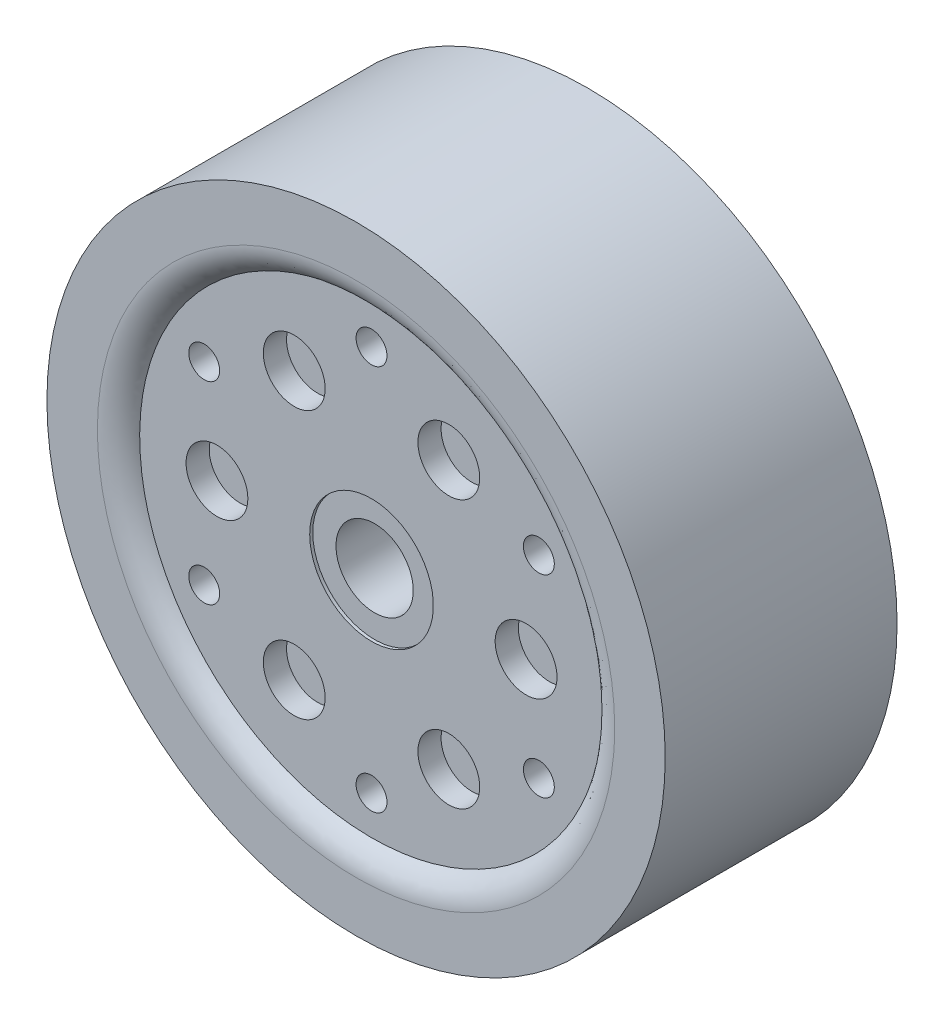
SolidWorks part; units mm, degrees
ref_plane "Plan de face" through (0, 0, 0) normal (0, 0, 1) x (1, 0, 0)
ref_plane "Plan de dessus" through (0, 0, 0) normal (0, 1, 0) x (1, 0, 0)
ref_plane "Plan de droite" through (0, 0, 0) normal (1, 0, 0) x (0, 0, -1)
sketch "Esquisse1" plane through (0, 0, 0) normal (0, 0, 1) x (1, 0, 0)
  circle A0 centre (0, 0) radius 20
  circle A1 centre (0, 0) radius 2.5
  circle A2 centre (0, 0) radius 4
  circle A4 centre (0, 0) radius 15
  circle A5 centre (0, 0) radius 17
extrude "Boss.-Extru.1" add sketch "Esquisse1" along normal blind 7.5 contours A0 A5 | A5 A4 region at (-19.4343, 0, 0) region at (-16.5192, 0, 0)
extrude "Boss.-Extru.2" add sketch "Esquisse1<3>" along normal blind 6.5 contours A4 region at (-14.5757, 0, 0)
sketch "Esquisse1<3>" plane through (0, 0, 0) normal (0, 0, 1) x (1, 0, 0) same geometry as "Esquisse1"
extrude "Boss.-Extru.3" add sketch "Esquisse1<6>" along normal blind 6.3 contours A2 A1 region at (-3.8869, 0, 0)
sketch "Esquisse1<6>" plane through (0, 0, 0) normal (0, 0, 1) x (1, 0, 0) same geometry as "Esquisse1"
fillet "Congé1" radius 2 1 edges at (15, 0, 7.5) first distance on face at (20, 0, 7.5)
sketch "Esquisse3" plane through (0, 0, 6.5) normal (0, 0, 1) x (1, 0, 0)
  line L0 (0, 0) -> (0, 12.5) construction
  line L1 (0, 0) -> (0, -12.5) construction
  line L2 (0, 0) -> (-10.8253, -6.25) construction
  line L3 (0, 0) -> (10.8253, -6.25) construction
  line L4 (0, 0) -> (10.8253, 6.25) construction
  line L5 (0, 0) -> (-10.8253, 6.25) construction
  circle A1 centre (0, 0) radius 12.5 construction
  circle A2 centre (0, 12.5) radius 1
  circle A3 centre (-10.8253, 6.25) radius 1
  circle A4 centre (-10.8253, -6.25) radius 1
  circle A5 centre (0, -12.5) radius 1
  circle A6 centre (10.8253, -6.25) radius 1
  circle A7 centre (10.8253, 6.25) radius 1
  dimension "D1" = 60
  dimension "D2" = 60
  dimension "D3" = 60
sketch "Esquisse4" plane through (0, 0, 6.5) normal (0, 0, 1) x (1, 0, 0)
  line L0 (0, 0) -> (10, 0) construction
  line L1 (10, 0) -> (-10, 0) construction
  line L2 (0, 0) -> (-5, 8.6603) construction
  line L3 (-5, 8.6603) -> (0, 0) construction
  line L4 (0, 0) -> (5, 8.6603) construction
  line L5 (5, 8.6603) -> (0, 0) construction
  line L6 (0, 0) -> (10, 0) construction
  line L7 (10, 0) -> (0, 0) construction
  line L8 (0, 0) -> (5, -8.6603) construction
  line L9 (5, -8.6603) -> (0, 0) construction
  line L10 (0, 0) -> (-5, -8.6603) construction
  circle A0 centre (0, 0) radius 10 construction
  circle A1 centre (-10, 0) radius 2
  circle A2 centre (-5, 8.6603) radius 2
  circle A3 centre (5, 8.6603) radius 2
  circle A4 centre (10, 0) radius 2
  circle A5 centre (5, -8.6603) radius 2
  circle A6 centre (-5, -8.6603) radius 2
extrude "Enlèv. mat.-Extru.1" cut sketch "Esquisse4" against normal blind 1.5
extrude "Enlèv. mat.-Extru.2" cut sketch "Esquisse3" against normal blind 7.5
mirror "Symétrie1" about plane through (0, 0, 0) normal (0, 0, 1) of "Enlèv. mat.-Extru.2", "Enlèv. mat.-Extru.1", "Boss.-Extru.3", "Boss.-Extru.2", "Boss.-Extru.1", "Congé1"
